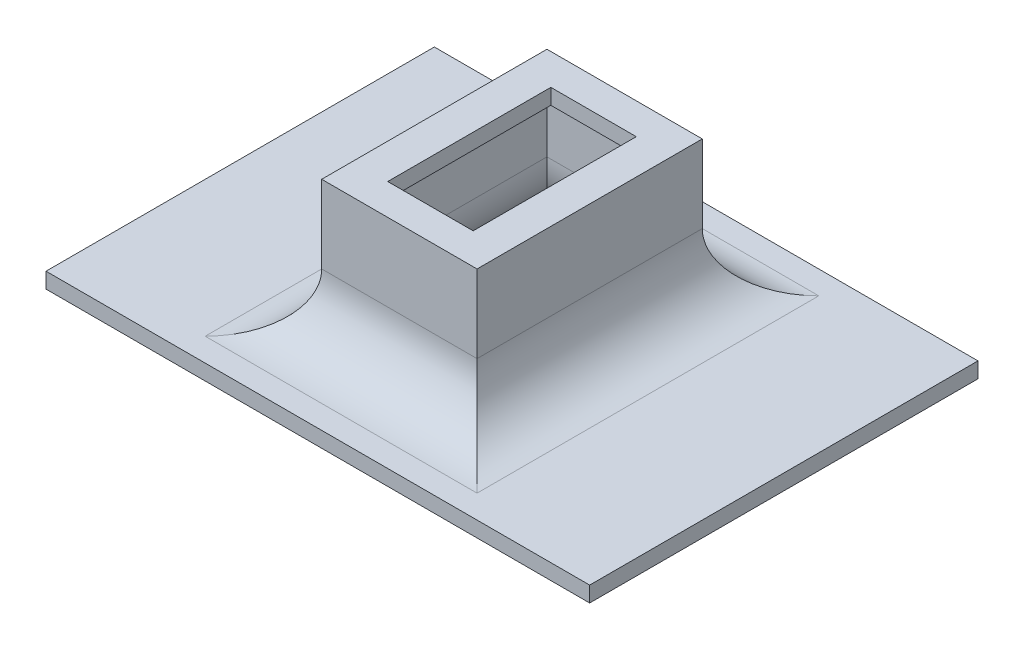
SolidWorks part; units mm, degrees
ref_plane "前基準面" through (0, 0, 0) normal (0, 0, 1) x (1, 0, 0)
ref_plane "上基準面" through (0, 0, 0) normal (0, 1, 0) x (1, 0, 0)
ref_plane "右基準面" through (0, 0, 0) normal (1, 0, 0) x (0, 0, -1)
sketch "Sketch2" plane through (0, 0, 0) normal (0, 1, 0) x (1, 0, 0)
  line L0 (0, 79.4767) -> (0, -94.4423) construction
  line L1 (-70, 50) -> (70, 50)
  line L2 (-70, 50) -> (-70, -50)
  line L3 (-70, -50) -> (70, -50)
  line L4 (70, 50) -> (70, -50)
  line L5 (0, -21.45) -> (0, 21.45) construction
  line L6 (-21.45, 0) -> (21.45, 0) construction
  line L7 (-83.6716, 0) -> (115.8704, 0) construction
  dimension "D1" = 140
  dimension "D2" = 100
extrude "Boss-Extrude1" add sketch "Sketch2" against normal blind 4
sketch "Sketch3" plane through (0, 0, 0) normal (0, 1, 0) x (1, 0, 0)
  line L0 (0, 46.5226) -> (0, -61.7702) construction
  line L1 (-20, 29) -> (20, 29)
  line L2 (-20, 29) -> (-20, -29)
  line L3 (-20, -29) -> (20, -29)
  line L4 (20, 29) -> (20, -29)
  line L5 (0, -21.45) -> (0, 21.45) construction
  line L6 (-75.545, 0) -> (103.7878, 0) construction
  line L7 (-21.45, 0) -> (21.45, 0) construction
  dimension "D1" = 40
  dimension "D2" = 58
extrude "Boss-Extrude2" add sketch "Sketch3" along normal blind 35
fillet "Fillet1" radius 15 4 edges at (-20, 0, 0) (0, 0, -29) (20, 0, 0) (0, 0, 29)
shell "Shell3" thickness 4 removed face at (0, -4, 0)
sketch "Sketch4" plane through (0, 35, 0) normal (0, 1, 0) x (1, 0, 0)
  line L0 (0, 45.1658) -> (0, -44.7952) construction
  line L1 (-11, 21) -> (11, 21)
  line L2 (-11, 21) -> (-11, -21)
  line L3 (-11, -21) -> (11, -21)
  line L4 (11, 21) -> (11, -21)
  line L5 (0, -21.45) -> (0, 21.45) construction
  line L6 (-61.3487, 0) -> (50.1074, 0) construction
  line L7 (-21.45, 0) -> (21.45, 0) construction
  dimension "D1" = 22
  dimension "D2" = 42
extrude "Cut-Extrude1" cut sketch "Sketch4" against normal through all
